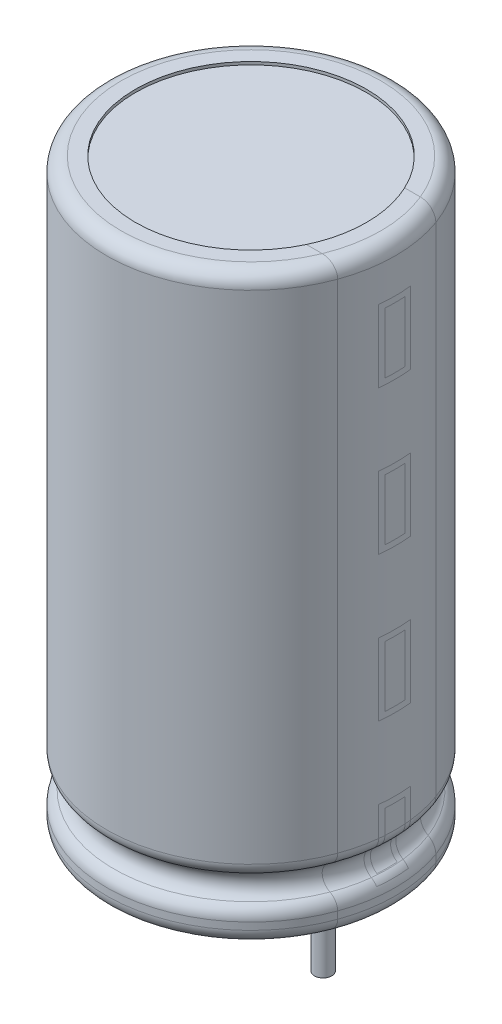
SolidWorks part; units mm, degrees
ref_plane "Front Plane" through (0, 0, 0) normal (0, 0, 1) x (1, 0, 0)
ref_plane "Top Plane" through (0, 0, 0) normal (0, 1, 0) x (1, 0, 0)
ref_plane "Right Plane" through (0, 0, 0) normal (1, 0, 0) x (0, 0, -1)
sketch "Sketch1" plane through (0, 0, 0) normal (0, 1, 0) x (1, 0, 0)
  line L0 (0, 0) -> (0, 44.7542) construction
  line L1 (0, 0) -> (-44.7542, 0) construction
  circle A0 centre (-2.5, 0) radius 0.3
  circle A1 centre (2.5, 0) radius 0.3
  dimension "D3" = 0.6
  dimension "D1" = 2.5
extrude "Boss-Extrude1" add sketch "Sketch1" against normal blind 3 and the other way blind 1
sketch "Sketch3" plane through (0, 0, 0) normal (0, 0, 1) x (1, 0, 0)
  line L1 (0, 0.1) -> (0, 20.2) construction
  line L2 (5, 0.5) -> (5, 0.75)
  line L3 (0, 0.1) -> (4, 0.1)
  line L4 (4, 20.2) -> (4.5, 20.2)
  line L5 (4, 0) -> (4.5, 0)
  line L6 (0, 20.1) -> (4, 20.1)
  line L7 (5, 2.4821) -> (5, 19.7)
  line L8 (4, 20.1) -> (4, 20.2)
  line L9 (5, 2.4821) -> (5, 20.2) construction
  line L10 (4, 0) -> (4, 0.1)
  line L11 (0, 20.1) -> (5, 20.1) construction
  line L12 (0, 20.2) -> (5, 20.2) construction
  line L13 (4, 2.4821) -> (4, 20.2) construction
  line L14 (0, 0.1) -> (0, 20.1)
  line L17 (0, 0.1) -> (5, 0.1) construction
  line L18 (0, 0) -> (5, 0) construction
  arc A0 (4.75, 2.049) -> (4.75, 1.183) centre (5, 1.616) ccw
  arc A1 (5, 0.75) -> (4.75, 1.183) centre (4.5, 0.75) ccw
  arc A2 (5, 2.4821) -> (4.75, 2.049) centre (4.5, 2.4821) cw
  arc A3 (5, 19.7) -> (4.5, 20.2) centre (4.5, 19.7) ccw
  arc A4 (4.5, 0) -> (5, 0.5) centre (4.5, 0.5) ccw
  point P13 (5, 2.116)
  point P29 (0, 20.1)
  point P30 (0, 0.1126)
  point P31 (0.1319, 0.1)
  point P32 (4.5, 1.616)
  point P33 (0.118, 20.2)
  point P35 (0, 0)
  point P36 (0.1461, 20.2)
  point P37 (-8.5502, 0.1)
  dimension "D2" = 0.5
  dimension "D1" = 0.5
  dimension "D9" = 0.5
  dimension "D3" = 20
  dimension "D6" = 5
  dimension "D7" = 0.1
  dimension "D8" = 8
  dimension "D10" = 0.25
  dimension "D11" = 9
  dimension "D5" = 1
revolve "Revolve1" add sketch "Sketch3" angle 360 about L14
sketch "Sketch4" plane through (0, 0, 0) normal (1, 0, 0) x (0, 0, -1)
  line L0 (-4.5, 0) -> (4.5, 0) construction
  line L1 (-1.7, 0) -> (1.7, 0)
  line L2 (0, 0) -> (0, 20.2) construction
  line L3 (-1.7, 20.2) -> (1.7, 20.2)
  line L4 (1.7, 0) -> (1.7, 20.2)
  line L5 (4, 20.2) -> (-4, 20.2) construction
  line L6 (-1.7, 0) -> (-1.7, 20.2)
  line L7 (-0.35, 13.3) -> (-0.35, 11.2)
  line L8 (-0.35, 13.3) -> (0.35, 13.3)
  line L9 (0, 13.3) -> (0, 11.2) construction
  line L10 (-0.35, 11.2) -> (0.35, 11.2)
  line L11 (0.35, 13.3) -> (0.35, 11.2)
  line L12 (0.55, 13.5) -> (0.55, 11)
  line L13 (-0.55, 11) -> (0.55, 11)
  line L14 (-0.55, 13.5) -> (-0.55, 11)
  line L15 (-0.55, 13.5) -> (0.55, 13.5)
  line L16 (0, 0) -> (0, -3.7489) construction
  line L17 (-0.35, 8.3) -> (-0.35, 6.2)
  line L18 (-0.35, 8.3) -> (0.35, 8.3)
  line L19 (-0.35, 6.2) -> (0.35, 6.2)
  line L20 (0.35, 8.3) -> (0.35, 6.2)
  line L21 (0.55, 8.5) -> (0.55, 6)
  line L22 (-0.55, 6) -> (0.55, 6)
  line L23 (-0.55, 8.5) -> (-0.55, 6)
  line L24 (-0.55, 8.5) -> (0.55, 8.5)
  line L25 (0, 8.3) -> (0, 6.2) construction
  line L26 (-0.35, 3.3) -> (-0.35, 1.2)
  line L27 (-0.35, 3.3) -> (0.35, 3.3)
  line L28 (-0.35, 1.2) -> (0.35, 1.2)
  line L29 (0.35, 3.3) -> (0.35, 1.2)
  line L30 (0.55, 3.5) -> (0.55, 1)
  line L31 (-0.55, 1) -> (0.55, 1)
  line L32 (-0.55, 3.5) -> (-0.55, 1)
  line L33 (-0.55, 3.5) -> (0.55, 3.5)
  line L34 (0, 3.3) -> (0, 1.2) construction
  line L35 (-0.55, 18.5) -> (0.55, 18.5)
  line L36 (-0.55, 18.5) -> (-0.55, 16)
  line L37 (-0.35, 18.3) -> (0.35, 18.3)
  line L38 (0.35, 18.3) -> (0.35, 16.2)
  line L39 (0.55, 18.5) -> (0.55, 16)
  line L40 (-0.35, 18.3) -> (-0.35, 16.2)
  line L41 (-0.35, 16.2) -> (0.35, 16.2)
  line L42 (-0.55, 16) -> (0.55, 16)
  line L51 (-0.55, 11) -> (-0.55, 8.5) construction
  line L52 (-0.55, 13.5) -> (-0.55, 16) construction
  point P20 (0, 0)
  point P23 (-0.6552, 20.4867)
  point P64 (0, 18.3)
  dimension "D5" = 3.4
  dimension "D6" = 0.2
  dimension "D7" = 1.1
  dimension "D8" = 2.1
  dimension "D1" = 0.7
  dimension "D9" = 1
  dimension "D10" = 2.5
  dimension "D2" = 3
  dimension "D3" = 2
split line "Split Line1"
